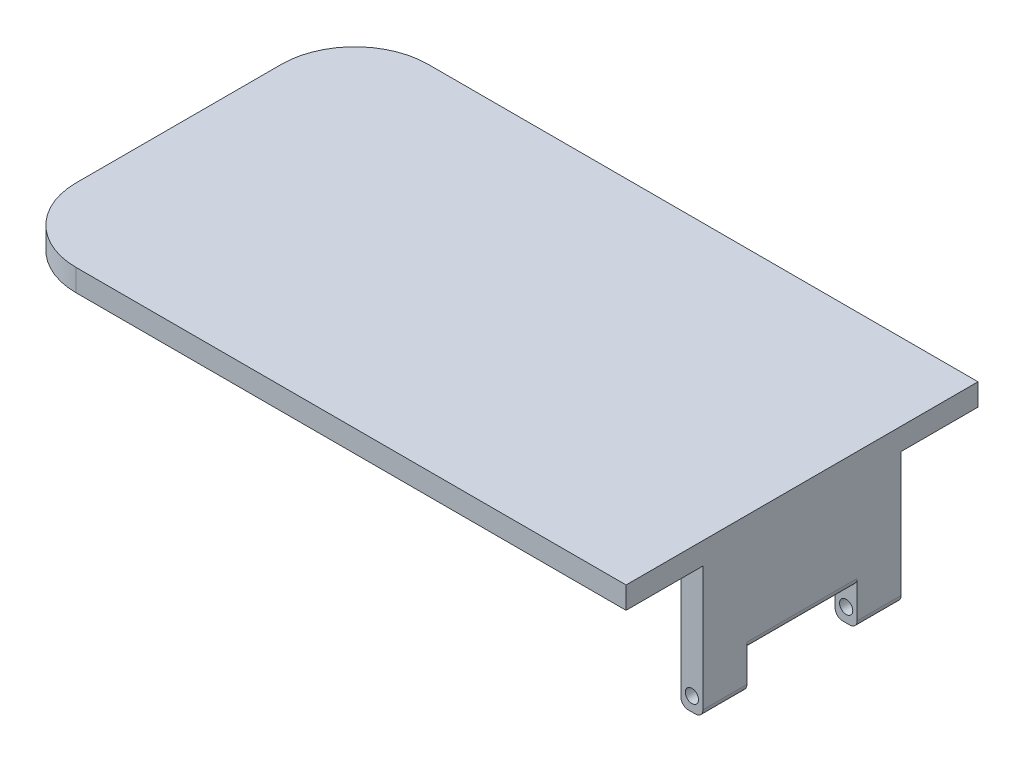
SolidWorks part; units mm, degrees
ref_plane "Front Plane" through (0, 0, 0) normal (0, 0, 1) x (1, 0, 0)
ref_plane "Top Plane" through (0, 0, 0) normal (0, 1, 0) x (1, 0, 0)
ref_plane "Right Plane" through (0, 0, 0) normal (1, 0, 0) x (0, 0, -1)
sketch "Sketch1" plane through (0, 0, 0) normal (0, 1, 0) x (1, 0, 0)
  line L1 (-42.5, 24) -> (42.5, 24)
  line L2 (-42.5, 24) -> (-42.5, -24)
  line L3 (-42.5, -24) -> (42.5, -24)
  line L4 (42.5, 24) -> (42.5, -24)
  line L5 (-42.5, 24) -> (42.5, -24) construction
  line L6 (-42.5, -24) -> (42.5, 24) construction
  point P0 (0, 0)
  dimension "D1" = 85
  dimension "D2" = 48
  dimension "D4" = 42.5
extrude "Boss-Extrude1" add sketch "Sketch1" against normal blind 3 contours L2 L3 L4 L1
sketch "Sketch2" plane through (0, -3, 0) normal (0, -1, 0) x (1, 0, 0)
  line L0 (-42.5, 24) -> (42.5, 24) construction
  line L1 (42.5, -24) -> (39.5, -24)
  line L2 (42.5, -24) -> (42.5, 24)
  line L3 (42.5, 24) -> (39.5, 24)
  line L4 (39.5, -24) -> (39.5, 24)
  dimension "D1" = 3
extrude "Boss-Extrude2" add sketch "Sketch2" along normal blind 18
sketch "Sketch5" plane through (0, 0, -24) normal (0, 0, -1) x (-1, 0, 0)
  line L0 (-39.5, -21) -> (-42.5, -21) construction
  circle A0 centre (-41, -19.1) radius 0.775
  point P4 (-41, -21)
  dimension "D1" = 1.55
  dimension "D2" = 1.9
hole_wizard "M1.6 Clearance Hole2" positions "Sketch8" profile "Sketch9" hole size "M1.6" standard "ISO" end condition through all
sketch "Sketch8" plane through (0, 0, -24) normal (0, 0, -1) x (-1, 0, 0)
  point P0 (-41, -19.1)
sketch "Sketch9" plane through (41, -19.1, -24) normal (1, 0, 0) x (0, 1, 0)
  line L0 (0, 0) -> (0, 48)
  line L1 (0, 48) -> (0.9, 48)
  line L2 (0.9, 48) -> (0.9, 0)
  line L5 (0.9, 0) -> (0, 0)
  line L11 (0, -6.35) -> (0, 107.95) construction
  dimension "Thru Hole Dia." = 1.8
  dimension "Thru Hole Depth" = 48
sketch "Sketch11" plane through (42.5, 0, 0) normal (1, 0, 0) x (0, 0, -1)
  line L0 (24, -21) -> (-24, -21) construction
  line L3 (-7.52, -16) -> (7.52, -16)
  line L5 (-7.52, -21) -> (7.52, -21)
  line L7 (-7.52, -16) -> (-7.52, -21)
  line L8 (7.52, -16) -> (7.52, -21)
  point P0 (0, -21)
  dimension "D1" = 5
  dimension "D2" = 15.04
extrude "Cut-Extrude5" cut sketch "Sketch11" against normal through all contours L5 L8 L3 L7
sketch "Sketch14" plane through (39.5, 0, 0) normal (-1, 0, 0) x (0, 0, 1)
  line L0 (-7.52, -21) -> (-24, -21) construction
  line L1 (-24, -3) -> (-13.52, -3)
  line L2 (-24, -3) -> (-24, -21)
  line L3 (-24, -21) -> (-13.52, -21)
  line L4 (-13.52, -3) -> (-13.52, -21)
  line L5 (24, -21) -> (7.52, -21) construction
  line L6 (24, -3) -> (13.52, -3)
  line L7 (24, -3) -> (24, -21)
  line L8 (24, -21) -> (13.52, -21)
  line L9 (13.52, -3) -> (13.52, -21)
  line L10 (24, -3) -> (-24, -3) construction
  line L11 (-7.52, -16) -> (-7.52, -21) construction
  dimension "D1" = 6
extrude "Cut-Extrude6" cut sketch "Sketch14" against normal through all contours L2 L1 L4 L3 | L7 L6 L9 L8
fillet "Fillet1" radius 1 1 edges at (42.5, -21, -10.52) type face fillet first side face at (42.5, -10.6667, 0) second side face at (41, -21, -10.52)
fillet "Fillet2" radius 1 1 edges at (42.5, -21, 10.52) type face fillet first side face at (42.5, -10.5, 0) second side face at (41, -21, 10.52)
fillet "Fillet3" radius 1 1 edges at (39.5, -21, -10.52) type face fillet first side face at (39.5, -15.25, 0) second side face at (40.5, -21, -10.52)
fillet "Fillet4" radius 1 1 edges at (39.5, -21, 10.52) type face fillet first side face at (39.5, -15, 0) second side face at (40.5, -21, 10.52)
fillet "Fillet5" radius 1 1 edges at (42.5, -16, 0) type face fillet first side face at (41, -16, 0) second side face at (42.5, -10.3333, 0)
fillet "Fillet6" radius 1 1 edges at (39.5, -16, 0) type face fillet first side face at (40.5, -16, 0) second side face at (39.5, -14.75, 0)
sketch "Sketch17" plane through (0, -3, 0) normal (0, -1, 0) x (1, 0, 0)
  line L1 (42.5, 24) -> (42.5, 13.52) construction
  circle A1 centre (2.21, 0) radius 23
  point P0 (2.21, 0)
  dimension "D1" = 40.29
  dimension "D2" = 46
extrude "Cut-Extrude11" cut sketch "Sketch17" against normal blind 1
fillet "Fillet9" radius 1 1 edges at (2.21, -3, -23)
fillet "Fillet10" radius 10 1 edges at (-42.5, -1.5, -24) type face fillet first side face at (-42.5, -1.5, 0) second side face at (0.442, -1.8, -24)
fillet "Fillet11" radius 10 1 edges at (-42.5, -1.5, 24) type face fillet first side face at (-42.5, -1.5, 5) second side face at (0.442, -1.8, 24)
sketch "Sketch18" plane through (0, -3, 0) normal (0, -1, 0) x (1, 0, 0)
  line L1 (-28.5, -6.8978) -> (-22.5, -6.8978)
  line L2 (-28.5, -6.8978) -> (-28.5, -2.5)
  line L3 (-28.5, -2.5) -> (-22.5, -2.5)
  line L4 (-22.5, -6.8978) -> (-22.5, -2.5)
  line L5 (-28.5, 2.5) -> (-22.5, 2.5)
  line L6 (-28.5, 2.5) -> (-28.5, 6.8572)
  line L7 (-28.5, 6.8572) -> (-22.5, 6.8572)
  line L8 (-22.5, 2.5) -> (-22.5, 6.8572)
  line L10 (-42.5, -14) -> (-42.5, 14) construction
  point P10 (-42.5, 0)
  point P13 (-38.7681, 3.1487)
  dimension "D1" = 5
  dimension "D2" = 2.5
  dimension "D3" = 14
  dimension "D4" = 14
  dimension "D5" = 6
  dimension "D6" = 6
extrude "Boss-Extrude3" add sketch "Sketch18" along normal blind 4
sketch "Sketch19" plane through (0, 0, 6.8572) normal (0, 0, 1) x (1, 0, 0)
  line L0 (-22.5, -3) -> (-28.5, -3) construction
  line L1 (-28.5, -7) -> (-28.5, -3) construction
  point P0 (-25.5, -5)
  dimension "D1" = 2
  dimension "D2" = 3
hole_wizard "Ø1.5 (1.5) Diameter Hole1" positions "Sketch20" profile "Sketch21" hole size "Ø1.5" standard "ISO" end condition through all
sketch "Sketch20" plane through (0, 0, 6.8572) normal (0, 0, 1) x (1, 0, 0)
  point P0 (-25.5, -5)
sketch "Sketch21" plane through (-25.5, -5, 6.8572) normal (1, 0, 0) x (0, -1, 0)
  line L0 (0, 0) -> (0, 30.8572)
  line L1 (0, 30.8572) -> (0.75, 30.8572)
  line L2 (0.75, 30.8572) -> (0.75, 0)
  line L5 (0.75, 0) -> (0, 0)
  line L11 (0, -6.35) -> (0, 107.95) construction
  dimension "Thru Hole Dia." = 1.5
  dimension "Thru Hole Depth" = 30.8572
